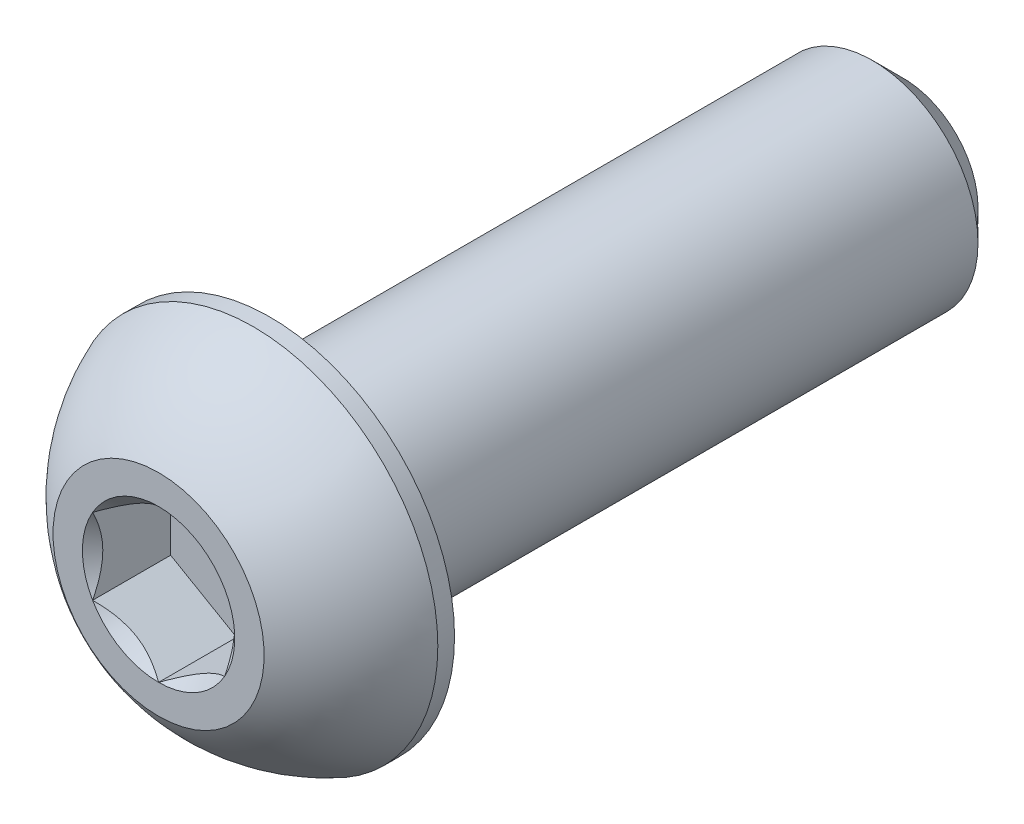
SolidWorks part; units mm, degrees
ref_plane "Front" through (0, 0, 0) normal (0, 0, 1) x (1, 0, 0)
ref_plane "Top" through (0, 0, 0) normal (0, 1, 0) x (1, 0, 0)
ref_plane "Right" through (0, 0, 0) normal (1, 0, 0) x (0, 0, -1)
sketch "Sketch1" plane through (0, 0, 0) normal (1, 0, 0) x (0, 0, -1)
  line L2 (3.3528, 3.175) -> (22.4028, 3.175)
  line L3 (22.4028, 3.175) -> (22.4028, 0)
  line L4 (22.4028, 0) -> (3.3528, 0)
  line L6 (2.8499, 5.5499) -> (3.3528, 5.5499) construction
  line L7 (22.4028, 3.175) -> (22.4028, -3.175) construction
  line L8 (0, 0) -> (3.3528, 0) construction
  line L9 (3.3528, 5.5499) -> (3.3528, -5.5499) construction
  line L11 (3.3528, 3.175) -> (3.3528, 0)
  line L13 (0, 1.9844) -> (0, -1.9844) construction
  line L14 (0, 1.9844) -> (0, 3.175) construction
  arc A3 (0, 3.175) -> (2.8499, 5.5499) centre (5.0603, 0) cw construction
  dimension "D1" = 0.5029
revolve "Revolve1" add sketch "Sketch1" angle 360 mid plane about L4
sketch "Sketch3" plane through (0, 0, -22.4028) normal (0, 0, -1) x (-1, 0, 0)
  circle A0 centre (0, 0) radius 3.175
curve "Helix/Spiral1" pitch 1.239 height 22.4028 turns 18.081
sketch "Sketch2" plane through (0, 0, 0) normal (1, 0, 0) x (0, 0, -1)
  line L0 (22.4028, 3.175) -> (23.4869, 3.175)
  line L1 (23.4869, 3.175) -> (23.0223, 2.3702)
  line L2 (23.0223, 2.3702) -> (22.8674, 2.3702)
  line L3 (22.8674, 2.3702) -> (22.4028, 3.175)
  line L4 (22.6351, 2.7726) -> (23.2546, 2.7726) construction
  dimension "D1" = 60
  dimension "D2" = 0.1549
  dimension "D3" = 0.6195
chamfer "Chamfer1" distance 0.9293 angle 45 1 edges at (0, 3.175, -22.4028)
sweep "Cut-Sweep1" [suppressed] cut profiles "Sketch2" path "Helix/Spiral1"
sketch "Sketch7" plane through (0, 0, 0) normal (1, 0, 0) x (0, 0, -1)
  line L6 (2.8499, 5.5499) -> (3.3528, 5.5499) construction
  line L8 (0, 0) -> (3.3528, 0) construction
  line L11 (3.3528, 5.5499) -> (3.3528, -5.5499) construction
  line L12 (2.8499, 5.5499) -> (3.3528, 5.5499)
  line L13 (0, 0) -> (3.3528, 0)
  line L14 (0, 1.9844) -> (0, -1.9844) construction
  line L15 (3.3528, 5.5499) -> (3.3528, 0)
  line L16 (0, 3.175) -> (0, 0)
  arc A2 (2.8499, 5.5499) -> (0, 3.175) centre (5.0603, 0) ccw construction
  arc A3 (2.8499, 5.5499) -> (0, 3.175) centre (5.0603, 0) ccw
revolve "Revolve2" add sketch "Sketch7" angle 360 mid plane about L13
sketch "Sketch5" plane through (0, 0, 0) normal (0, 0, 1) x (1, 0, 0)
  line L1 (1.9844, -1.1457) -> (1.9844, 1.1457)
  line L2 (1.9844, 1.1457) -> (0, 2.2914)
  line L3 (0, 2.2914) -> (-1.9844, 1.1457)
  line L4 (-1.9844, 1.1457) -> (-1.9844, -1.1457)
  line L5 (-1.9844, -1.1457) -> (0, -2.2914)
  line L6 (0, -2.2914) -> (1.9844, -1.1457)
  circle A0 centre (0, 0) radius 1.9844 construction
extrude "Cut-Extrude2" cut sketch "Sketch5" against normal blind 2.347
sketch "Sketch6" plane through (0, 0, 0) normal (0, 0, 1) x (1, 0, 0)
  circle A0 centre (0, 0) radius 2.2914
extrude "Cut-Extrude3" cut sketch "Sketch6" against normal blind 2.347 draft 45
sketch "Sketch9" [suppressed] plane through (0, 0, -3.3528) normal (0, 0, 1) x (1, 0, 0)
  circle A2 centre (0, 0) radius 3.175
extrude "Boss-Extrude2" [suppressed] add sketch "Sketch9" against normal offset from surface (76.2 mm away) 22.225 up to face at (0, 2.2457, -22.4028)
sketch "Sketch10" plane through (0, 0, 0) normal (1, 0, 0) x (0, 0, -1)
  line L0 (22.4028, 3.175) -> (22.4028, -3.175) construction
  point P0 (20.5443, -3.175)
  dimension "D1" = 1.8585
equation "\"D3@Helix/Spiral1\" = \"Lg@Sketch1\" + \"Head Ht@Sketch1\""
equation "\"D2@Sketch2\" = \"D4@Helix/Spiral1\" * .125"
equation "\"D3@Sketch2\" = \"D4@Helix/Spiral1\" * .5"
equation "\"D1@Chamfer1\" = \"D4@Helix/Spiral1\" * .75"
equation "\"D1@Cut-Extrude2\" = \"Head Ht@Sketch1\" * .7"
equation "\"D1@Sketch1\" = \"Head Ht@Sketch1\" * .15"
equation "\"D1@Sketch10\" = \"D4@Helix/Spiral1\" * 1.5"
equation "\"D1@Cut-Extrude3\" = \"D1@Cut-Extrude2\""
